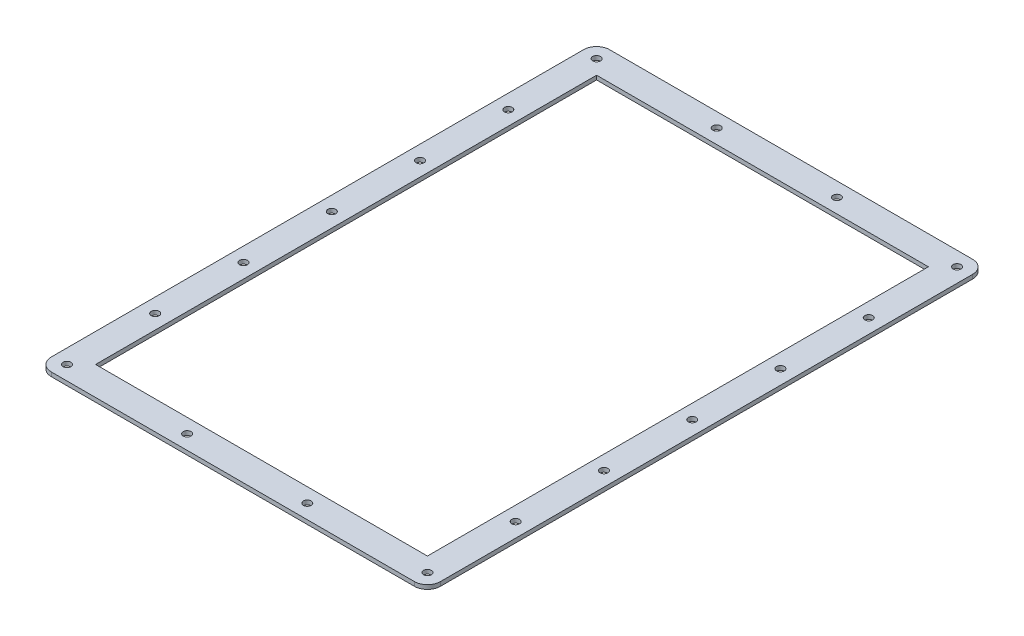
SolidWorks part; units mm, degrees
material "5052-H32"
ref_plane "Front Plane" through (0, 0, 0) normal (0, 0, 1) x (1, 0, 0)
ref_plane "Top Plane" through (0, 0, 0) normal (0, 1, 0) x (1, 0, 0)
ref_plane "Right Plane" through (0, 0, 0) normal (1, 0, 0) x (0, 0, -1)
sketch "Sketch1" plane through (0, 0, 0) normal (0, 1, 0) x (1, 0, 0)
  line L0 (-147, 157) -> (152, 157)
  line L1 (-125, -250) -> (130, -250)
  line L2 (-125, -250) -> (-125, 135)
  line L3 (-125, 135) -> (130, 135)
  line L4 (130, -250) -> (130, 135)
  line L5 (-125, -250) -> (130, 135) construction
  line L6 (-125, 135) -> (130, -250) construction
  line L7 (152, -272) -> (152, 157)
  line L8 (-147, -272) -> (152, -272)
  line L9 (-147, -272) -> (-147, 157)
  line L12 (130, -57.5) -> (-125, -57.5) construction
  circle A34 centre (141, 146) radius 3
  circle A35 centre (48.6667, 146) radius 3
  circle A36 centre (-43.6667, 146) radius 3
  circle A37 centre (-136, 146) radius 3
  circle A90 centre (141, 78.1667) radius 3
  circle A91 centre (141, 10.3333) radius 3
  circle A92 centre (141, -57.5) radius 3
  circle A93 centre (141, -125.3333) radius 3
  circle A94 centre (141, -193.1667) radius 3
  circle A102 centre (-136, 78.1667) radius 3
  circle A103 centre (141, -261) radius 3
  circle A106 centre (-136, 10.3333) radius 3
  circle A107 centre (48.6667, -261) radius 3
  circle A110 centre (-136, -57.5) radius 3
  circle A111 centre (-43.6667, -261) radius 3
  circle A114 centre (-136, -125.3333) radius 3
  circle A115 centre (-136, -261) radius 3
  circle A118 centre (-136, -193.1667) radius 3
  circle A119 centre (48.6667, -125.3333) radius 3 [skipped]
  circle A120 centre (-43.6667, -125.3333) radius 3 [skipped]
  circle A121 centre (48.6667, 78.1667) radius 3 [skipped]
  circle A122 centre (-43.6667, 78.1667) radius 3 [skipped]
  circle A123 centre (48.6667, 10.3333) radius 3 [skipped]
  circle A124 centre (48.6667, -57.5) radius 3 [skipped]
  circle A125 centre (-43.6667, -57.5) radius 3 [skipped]
  circle A126 centre (-43.6667, 10.3333) radius 3 [skipped]
  circle A127 centre (48.6667, -193.1667) radius 3 [skipped]
  circle A128 centre (-43.6667, -193.1667) radius 3 [skipped]
  dimension "D4" = 6
  dimension "D2" = 385
  dimension "D1" = 22
  dimension "D3" = 255
  dimension "D5" = 11
  dimension "D6" = 11
  dimension "D9" = 67.8333
  dimension "D10" = 92.3333
  dimension "D7" = 4
  dimension "D8" = 7
extrude "Boss-Extrude1" add sketch "Sketch1" along normal blind 3.175 contours L9 L8 L7 L0 L4 L1 L2 L3 A34 region at (2.5, 0, -151.7708)
fillet "Fillet1" radius 10 4 edges at (152, 1.5875, 272) (-147, 1.5875, 272) (152, 1.5875, -157) (-147, 1.5875, -157)
equation "\"L\"= 385"
equation "\"W\"= 255"
equation "\"H\"= 110"
equation "\"Compartment Width\"= 80"
equation "\"T\"= 4.7625 * 2 / 3"
equation "\"Inside Fillet Radius\"= 5.55625"
equation "\"Hole\"=15"
equation "\"D2@Sketch1\"=\"L\""
equation "\"D1@Boss-Extrude1\"=\"T\""
equation "\"D3@Sketch1\"=\"W\""
equation "\"D9@Sketch1\"=(\"L\"+22)/6"
equation "\"D10@Sketch1\"=(\"W\"+22)/3"
equation "\"Offset\"= 30"
equation "\"Wheel to Wall\"= 50"
